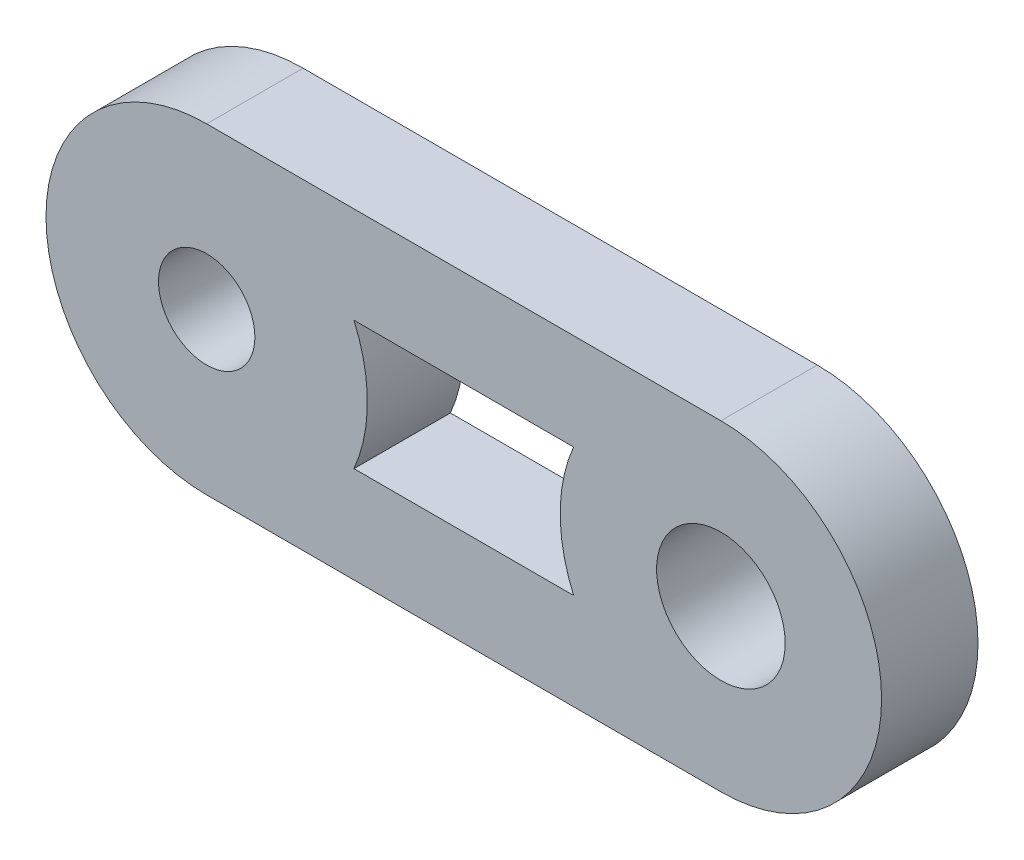
SolidWorks part; units mm, degrees
material "1060 Alloy"
ref_plane "Front Plane" through (0, 0, 0) normal (0, 0, 1) x (1, 0, 0)
ref_plane "Top Plane" through (0, 0, 0) normal (0, 1, 0) x (1, 0, 0)
ref_plane "Right Plane" through (0, 0, 0) normal (1, 0, 0) x (0, 0, -1)
sketch "Sketch1" plane through (0, 0, 0) normal (0, 0, 1) x (1, 0, 0)
  line L0 (0, 0) -> (16, 0)
  line L1 (0, -5) -> (16, -5)
  line L2 (0, 5) -> (16, 5)
  circle A0 centre (16, 0) radius 1.5
  circle A1 centre (0, 0) radius 1.5
  arc A2 (0, -5) -> (0, 5) centre (0, 0) cw
  arc A3 (16, -5) -> (16, 5) centre (16, 0) ccw
  dimension "D2" = 3
  dimension "D1" = 3
extrude "Extrude1" add sketch "Sketch1" along normal blind 3 contours L1 A3 L2 A2 A1 A0 region at (-4.7214, 0, 0)
sketch "Sketch2" plane through (0, 0, 3) normal (0, 0, 1) x (1, 0, 0)
  line L4 (0, -2) -> (16, -2)
  line L5 (16, 2) -> (0, 2)
  line L6 (4.5826, -2) -> (11.4174, -2)
  line L7 (11.4174, 2) -> (4.5826, 2)
  circle A0 centre (16, 0) radius 2
  arc A2 (4.5826, -2) -> (4.5826, 2) centre (0, 0) ccw
  arc A3 (11.4174, 2) -> (11.4174, -2) centre (16, 0) ccw
  arc A4 (16, -2) -> (16, 2) centre (16, 0) ccw
  arc A5 (0, 2) -> (0, -2) centre (0, 0) ccw
  dimension "D2" = 4
  dimension "D1" = 3
extrude "Cut-Extrude1" cut sketch "Sketch2" against normal blind 10
move or copy body "Body-Move/Copy1" [suppressed] bodies to move or copy 103
move or copy body "Body-Move/Copy2" [suppressed] bodies to move or copy 103
